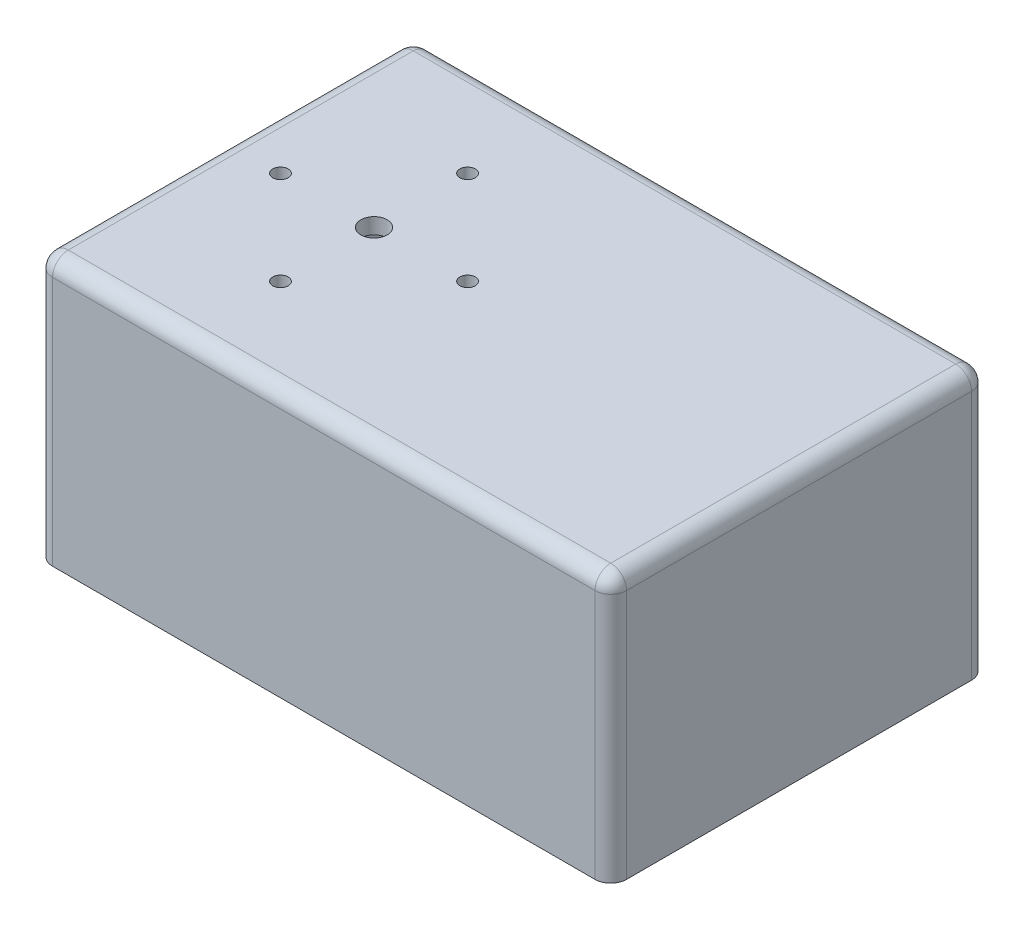
SolidWorks part; units mm, degrees
ref_plane "Front Plane" through (0, 0, 0) normal (0, 0, 1) x (1, 0, 0)
ref_plane "Top Plane" through (0, 0, 0) normal (0, 1, 0) x (1, 0, 0)
ref_plane "Right Plane" through (0, 0, 0) normal (1, 0, 0) x (0, 0, -1)
sketch "Sketch1" plane through (0, 0, 0) normal (0, 1, 0) x (1, 0, 0)
  line L1 (-109, 71.5) -> (109, 71.5)
  line L2 (-109, 71.5) -> (-109, -71.5)
  line L3 (-109, -71.5) -> (109, -71.5)
  line L4 (109, 71.5) -> (109, -71.5)
  line L5 (-109, 71.5) -> (109, -71.5) construction
  line L6 (-109, -71.5) -> (109, 71.5) construction
  point P0 (0, 0)
  dimension "D1" = 218
  dimension "D2" = 143
extrude "Boss-Extrude1" add sketch "Sketch1" along normal blind 101
fillet "Fillet1" radius 6 8 edges at (-109, 50.5, -71.5) (109, 50.5, -71.5) (109, 50.5, 71.5) (-109, 50.5, 71.5) (-109, 101, 0) (0, 101, -71.5) (109, 101, 0) (0, 101, 71.5)
shell "Shell1" thickness 6 removed face at (0, 0, 0)
sketch "Sketch2" plane through (0, 101, 0) normal (0, 1, 0) x (1, 0, 0)
  line L0 (-57.4, 0) -> (-109, 0) construction
  line L1 (-85, 0) -> (-57.4, 0) construction
  line L3 (-109, -65.5) -> (-109, 65.5) construction
  circle A0 centre (-52.4, 0) radius 5
  circle A1 centre (-52.4, 0) radius 35.525 construction
  circle A2 centre (-52.4, 35.525) radius 2.925
  circle A3 centre (-87.925, 0) radius 2.925
  circle A4 centre (-52.4, -35.525) radius 2.925
  circle A5 centre (-16.875, 0) radius 2.925
  dimension "D1" = 10
  dimension "D3" = 5.85
  dimension "D4" = 27.6
  dimension "D2" = 51.6
extrude "Cut-Extrude1" cut sketch "Sketch2" against normal through all
